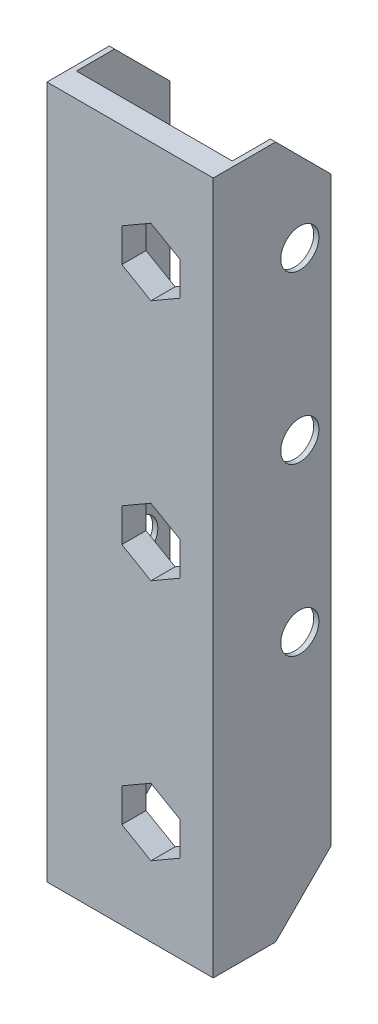
SolidWorks part; units mm, degrees
ref_plane "Front" through (0, 0, 0) normal (0, 0, 1) x (1, 0, 0)
ref_plane "Top" through (0, 0, 0) normal (0, 1, 0) x (1, 0, 0)
ref_plane "Right" through (0, 0, 0) normal (1, 0, 0) x (0, 0, -1)
sketch "Sketch1" plane through (0, 0, 0) normal (0, 1, 0) x (1, 0, 0)
  line L0 (0, 0) -> (0, 17)
  line L1 (0, 17) -> (0.75, 17)
  line L2 (0.75, 17) -> (0.75, 3.5)
  line L3 (0.75, 3.5) -> (23.25, 3.5)
  line L4 (23.25, 3.5) -> (23.25, 17)
  line L5 (23.25, 17) -> (24, 17)
  line L6 (24, 17) -> (24, 0)
  line L7 (24, 0) -> (0, 0)
  dimension "D1" = 3.5
  dimension "D2" = 0.75
  dimension "D3" = 24
  dimension "D4" = 17
extrude "Boss-Extrude1" add sketch "Sketch1" along normal blind 100 contours L3 L4 L5 L6 L7 L0 L1 L2
sketch "Sketch2" plane through (0, 0, 0) normal (0, 0, 1) x (1, 0, 0)
  line L0 (24, 100) -> (0, 100) construction
  line L1 (15, 80.1503) -> (19.2, 82.5751)
  line L2 (19.2, 82.5751) -> (19.2, 87.4249)
  line L3 (19.2, 87.4249) -> (15, 89.8497)
  line L4 (15, 89.8497) -> (10.8, 87.4249)
  line L5 (10.8, 87.4249) -> (10.8, 82.5751)
  line L6 (10.8, 82.5751) -> (15, 80.1503)
  line L7 (15, 45.1503) -> (19.2, 47.5751)
  line L8 (19.2, 47.5751) -> (19.2, 52.4249)
  line L9 (19.2, 52.4249) -> (15, 54.8497)
  line L10 (15, 54.8497) -> (10.8, 52.4249)
  line L11 (10.8, 52.4249) -> (10.8, 47.5751)
  line L12 (10.8, 47.5751) -> (15, 45.1503)
  line L13 (15, 19.8497) -> (10.8, 17.4249)
  line L14 (10.8, 17.4249) -> (10.8, 12.5751)
  line L15 (10.8, 12.5751) -> (15, 10.1503)
  line L16 (15, 10.1503) -> (19.2, 12.5751)
  line L17 (19.2, 12.5751) -> (19.2, 17.4249)
  line L18 (19.2, 17.4249) -> (15, 19.8497)
  line L19 (24, 100) -> (24, 0) construction
  circle A0 centre (15, 85) radius 4.2 construction
  circle A1 centre (15, 50) radius 4.2 construction
  circle A2 centre (15, 15) radius 4.2 construction
  dimension "D1" = 35
  dimension "D2" = 35
  dimension "D3" = 15
  dimension "D4" = 8.4
  dimension "D5" = 9
extrude "Cut-Extrude1" cut sketch "Sketch2" against normal through all both and the other way through all contours L11 L12 L7 L8 L9 L10 | L17 L18 L13 L14 L15 L16 | L5 L6 L1 L2 L3 L4 region at (15, 85, 0) region at (15, 50, 0) region at (15, 15, 0)
hole_wizard "M5 Clearance Hole1" positions "Sketch3" profile "Sketch4" hole size "M5" standard "ISO" end condition through all
sketch "Sketch3" plane through (24, 0, 0) normal (1, 0, 0) x (0, 0, -1)
  line L0 (17, 100) -> (0, 100) construction
  line L2 (3.5, 100) -> (3.5, 0) construction
  point P0 (12.5, 85)
  point P2 (12.5, 37)
  point P4 (12.5, 61)
  dimension "D1" = 24
  dimension "D2" = 24
  dimension "D3" = 15
  dimension "D4" = 9
sketch "Sketch4" plane through (24, 85, -12.5) normal (0, 1, 0) x (0, 0, -1)
  line L0 (0, 0) -> (0, 24)
  line L1 (0, 24) -> (2.75, 24)
  line L2 (2.75, 24) -> (2.75, 0)
  line L5 (2.75, 0) -> (0, 0)
  line L11 (0, -6.35) -> (0, 107.95) construction
  dimension "Thru Hole Dia." = 5.5
  dimension "Thru Hole Depth" = 24
chamfer "Chamfer1" distance 8 angle 45 4 edges at (0.375, 100, -17) (23.625, 100, -17) (23.625, 0, -17) (0.375, 0, -17)
